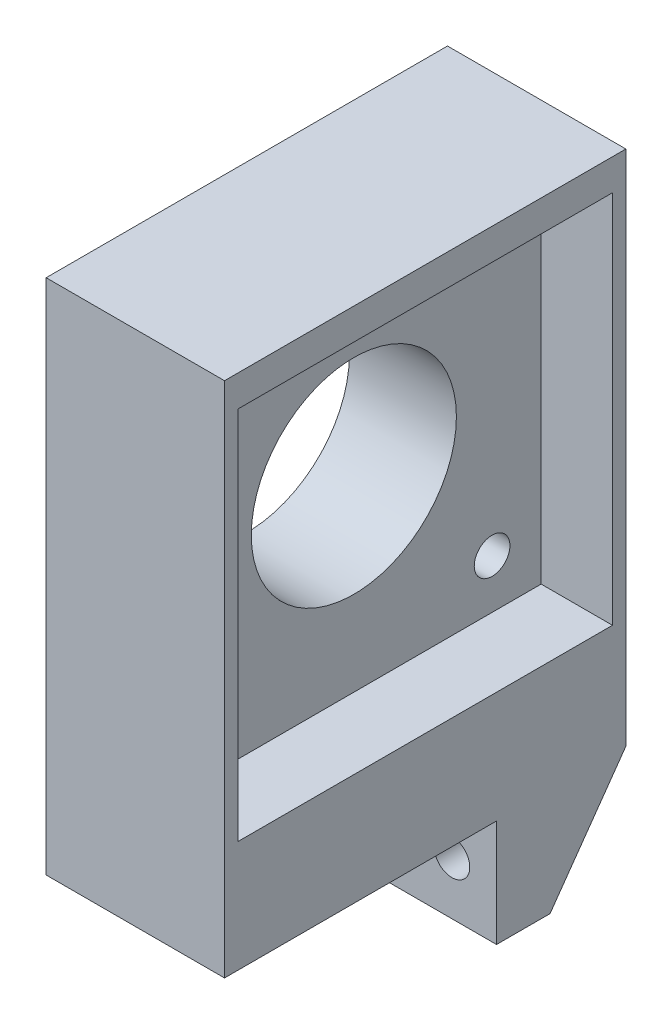
SolidWorks part; units mm, degrees
ref_plane "Front Plane" through (0, 0, 0) normal (0, 0, 1) x (1, 0, 0)
ref_plane "Top Plane" through (0, 0, 0) normal (0, 1, 0) x (1, 0, 0)
ref_plane "Right Plane" through (0, 0, 0) normal (1, 0, 0) x (0, 0, -1)
sketch "Sketch1" plane through (0, 0, 0) normal (0, 1, 0) x (1, 0, 0)
  line L1 (0, 0) -> (-20, 0)
  line L2 (0, 0) -> (0, -45)
  line L3 (0, -45) -> (-20, -45)
  line L4 (-20, 0) -> (-20, -45)
  dimension "D1" = 20
  dimension "D2" = 45
extrude "Boss-Extrude1" add sketch "Sketch1" along normal blind 70
sketch "Sketch2" plane through (0, 0, 0) normal (1, 0, 0) x (0, 0, -1)
  line L0 (-45, 70) -> (0, 70) construction
  line L1 (0, 70) -> (0, 0) construction
  line L2 (0, 45.5) -> (-45, 45.5) construction
  line L3 (-22.5, 70) -> (-22.5, 0) construction
  line L4 (-22.5, 70) -> (-22.5, 0) construction
  line L7 (-45, 70) -> (-45, 0) construction
  circle A0 centre (-7, 61) radius 2
  circle A4 centre (-22.5, 45.5) radius 11.5
  circle A5 centre (-7, 30) radius 2
  circle A8 centre (-38, 30) radius 2
  circle A9 centre (-38, 61) radius 2
  dimension "D1" = 4
  dimension "D2" = 9
  dimension "D3" = 15.5
  dimension "D6" = 23
  dimension "D7" = 0
  dimension "D8" = 0
  dimension "D4" = 15.5
  dimension "D5" = 0
extrude "Cut-Extrude2" cut sketch "Sketch2" against normal blind 60
sketch "Sketch4" plane through (0, 0, 0) normal (1, 0, 0) x (0, 0, -1)
  line L1 (-45, 0) -> (-14.5, 0)
  line L2 (-45, 0) -> (-45, 12)
  line L3 (-45, 12) -> (-14.5, 12)
  line L4 (-14.5, 0) -> (-14.5, 12)
  circle A0 centre (-22.5, 45.5) radius 11.5 construction
  dimension "D1" = 12
  dimension "D2" = 8
extrude "Cut-Extrude3" cut sketch "Sketch4" against normal blind 60
sketch "Sketch8" plane through (0, 0, 0) normal (0, 0, -1) x (-1, 0, 0)
  line L0 (0, 0) -> (20, 0) construction
  line L1 (20, 70) -> (20, 0) construction
  line L2 (0, 70) -> (0, 0) construction
  circle A0 centre (15, 6) radius 2
  circle A1 centre (5, 6) radius 2
  dimension "D1" = 4
  dimension "D2" = 6
  dimension "D3" = 5
  dimension "D4" = 4
  dimension "D5" = 0
  dimension "D6" = 5
extrude "Cut-Extrude5" cut sketch "Sketch8" against normal blind 15
sketch "Sketch9" plane through (0, 0, 0) normal (1, 0, 0) x (0, 0, -1)
  line L0 (0, 50) -> (-45, 41) construction
  line L1 (-1.5, 66.5) -> (-43.5, 66.5)
  line L2 (-1.5, 66.5) -> (-1.5, 24.5)
  line L3 (-1.5, 24.5) -> (-43.5, 24.5)
  line L4 (-43.5, 66.5) -> (-43.5, 24.5)
  line L5 (0, 70) -> (0, 0) construction
  line L6 (-45, 70) -> (-45, 12) construction
  line L7 (-22.5, 70) -> (-22.5, 12) construction
  line L8 (-45, 70) -> (0, 70) construction
  line L9 (-14.5, 12) -> (-45, 12) construction
  circle A0 centre (-22.5, 45.5) radius 11.5 construction
  dimension "D1" = 0
  dimension "D2" = 42
  dimension "D3" = 21
  dimension "D4" = 42
  dimension "D5" = 21
  dimension "D6" = 0
extrude "Cut-Extrude6" cut sketch "Sketch9" against normal blind 8
sketch "Sketch11" plane through (0, 0, 0) normal (1, 0, 0) x (0, 0, -1)
  line L7 (-8.5, 0) -> (0, 0)
  line L8 (-14.5, 0) -> (0, 0) construction
  line L9 (0, 0) -> (0, 12)
  line L10 (0, 70) -> (0, 0) construction
  line L11 (0, 12) -> (-8.5, 0)
  line L12 (-14.5, 12) -> (-45, 12) construction
  dimension "D1" = 0
  dimension "D2" = 6
extrude "Cut-Extrude8" cut sketch "Sketch11" against normal blind 30
sketch "Sketch17" plane through (0, 0, 0) normal (0, 0, -1) x (-1, 0, 0)
  circle A0 centre (15, 6) radius 3.5
  circle A1 centre (5, 6) radius 3.5
  dimension "D1" = 7
  dimension "D2" = 7
extrude "Cut-Extrude13" cut sketch "Sketch17" against normal blind 9.1811
